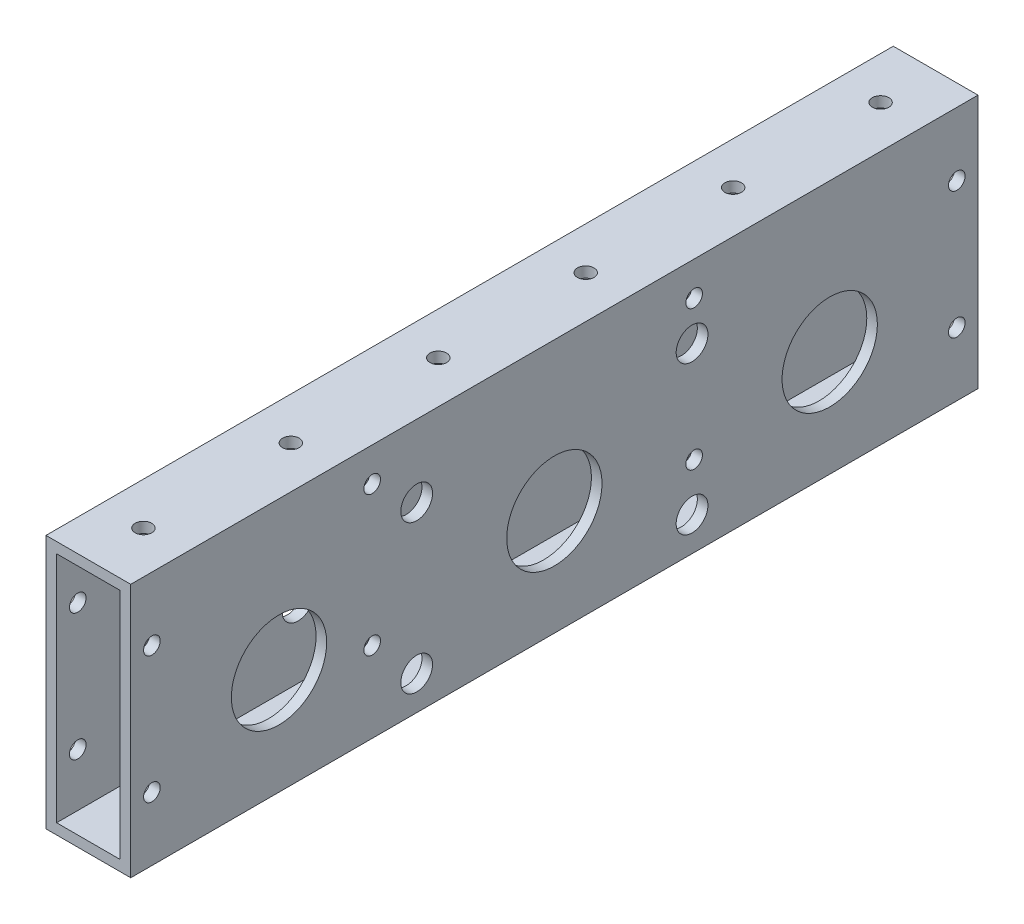
SolidWorks part; units mm, degrees
material "6061-T6 (SS)"
ref_plane "Front Plane" through (0, 0, 0) normal (0, 0, 1) x (1, 0, 0)
ref_plane "Top Plane" through (0, 0, 0) normal (0, 1, 0) x (1, 0, 0)
ref_plane "Right Plane" through (0, 0, 0) normal (1, 0, 0) x (0, 0, -1)
sketch "Sketch1" plane through (0, 0, 0) normal (1, 0, 0) x (0, 0, -1)
  line L1 (-127, 38.1) -> (127, 38.1)
  line L2 (-127, 38.1) -> (-127, -38.1)
  line L3 (-127, -38.1) -> (127, -38.1)
  line L4 (127, 38.1) -> (127, -38.1)
  line L5 (-127, 38.1) -> (127, -38.1) construction
  line L6 (-127, -38.1) -> (127, 38.1) construction
  point P0 (0, 0)
  dimension "D1" = 76.2
  dimension "D2" = 254
extrude "Boss-Extrude1" add sketch "Sketch1" along normal blind 25.4
shell "Shell1" thickness 3.175 removed face at (12.7, 0, -127) removed face at (12.7, 0, 127)
sketch "Sketch2" plane through (25.4, 0, 0) normal (1, 0, 0) x (0, 0, -1)
  line L0 (-127, -38.1) -> (127, -38.1) construction
  line L1 (127, 38.1) -> (-127, 38.1) construction
  line L2 (-41.275, -27.94) -> (41.275, -27.94) construction
  line L3 (-41.275, -27.94) -> (-41.275, 16.51) construction
  line L4 (-41.275, 16.51) -> (41.275, 16.51) construction
  line L5 (41.275, -27.94) -> (41.275, 16.51) construction
  line L6 (-41.275, -27.94) -> (41.275, 16.51) construction
  line L7 (-41.275, 16.51) -> (41.275, -27.94) construction
  line L9 (-54.61, 27.94) -> (41.91, 27.94) construction
  line L10 (-54.61, 27.94) -> (-54.61, -13.97) construction
  line L11 (-54.61, -13.97) -> (41.91, -13.97) construction
  line L12 (41.91, 27.94) -> (41.91, -13.97) construction
  circle A0 centre (0, -6.35) radius 14.2875
  circle A1 centre (-82.55, -6.35) radius 14.2875
  circle A2 centre (82.55, -6.35) radius 14.2875
  circle A3 centre (-82.55, -6.35) radius 38.1 construction
  circle A4 centre (0, -6.35) radius 38.1 construction
  circle A5 centre (82.55, -6.35) radius 38.1 construction
  circle A6 centre (-41.275, 16.51) radius 2.4892
  circle A7 centre (-41.275, -27.94) radius 2.4892
  circle A8 centre (41.275, -27.94) radius 2.4892
  circle A9 centre (41.275, 16.51) radius 2.4892
  circle A10 centre (-54.61, 27.94) radius 2.4892
  circle A11 centre (-54.61, -13.97) radius 2.4892
  circle A12 centre (41.91, -13.97) radius 2.4892
  circle A13 centre (41.91, 27.94) radius 2.4892
  point P11 (0, 0)
  point P12 (0, -5.715)
  dimension "D1" = 28.575
  dimension "D5" = 76.2
  dimension "D10" = 4.9784
  dimension "D2" = 31.75
  dimension "D3" = 82.55
  dimension "D4" = 82.55
  dimension "D6" = 0
  dimension "D7" = 10.16
  dimension "D8" = 21.59
  dimension "D9" = 82.55
  dimension "D11" = 10.16
  dimension "D12" = 96.52
  dimension "D13" = 41.91
  dimension "D14" = 24.13
extrude "Cut-Extrude1" cut sketch "Sketch2" against normal through all
sketch "Sketch3" plane through (25.4, 0, 0) normal (1, 0, 0) x (0, 0, -1)
  line L0 (-120.65, 19.05) -> (-120.65, -19.05) construction
  line L1 (-127, 38.1) -> (-127, -38.1) construction
  point P2 (-120.65, 0)
  point P3 (-127, 0)
  dimension "D1" = 38.1
  dimension "D2" = 6.35
hole_wizard "#10 Clearance Hole1" positions "Sketch4" profile "Sketch6" hole size "#10" standard "ANSI Inch" end condition through all
sketch "Sketch4" plane through (25.4, 0, 0) normal (1, 0, 0) x (0, 0, -1)
  point P0 (-120.65, 19.05)
  point P3 (-120.65, -19.05)
sketch "Sketch6" plane through (25.4, 19.05, 120.65) normal (0, 1, 0) x (0, 0, -1)
  line L0 (0, 0) -> (0, 25.4)
  line L1 (0, 25.4) -> (2.4892, 25.4)
  line L2 (2.4892, 25.4) -> (2.4892, 0)
  line L5 (2.4892, 0) -> (0, 0)
  line L11 (0, -6.35) -> (0, 107.95) construction
  dimension "Thru Hole Dia." = 4.9784
  dimension "Thru Hole Depth" = 25.4
mirror "Mirror1" about plane through (0, 0, 0) normal (0, 0, 1) of "#10 Clearance Hole1"
hole_wizard "3/8 (0.375) Diameter Hole1" positions "Sketch7" profile "Sketch8" hole size "3/8" standard "ANSI Inch"
sketch "Sketch7" plane through (0, 0, 0) normal (-1, 0, 0) x (0, 0, 1)
  point P0 (54.61, 27.94)
  point P3 (54.61, -13.97)
  point P6 (-41.91, -13.97)
  point P9 (-41.91, 27.94)
sketch "Sketch8" plane through (0, 27.94, 54.61) normal (0, 1, 0) x (0, 0, 1)
  line L0 (0, 0) -> (0, 13.7836)
  line L1 (0, 13.7836) -> (4.7625, 10.922)
  line L2 (4.7625, 10.922) -> (4.7625, 0)
  line L5 (4.7625, 0) -> (0, 0)
  line L10 (0, 13.7836) -> (-4.7625, 10.922) construction
  line L11 (0, -6.35) -> (0, 107.95) construction
  dimension "Hole Dia." = 9.525
  dimension "Hole Depth" = 10.922
  dimension "Drill Angle" = 118
hole_wizard "3/8 (0.375) Diameter Hole2" positions "Sketch9" profile "Sketch10" hole size "3/8" standard "ANSI Inch"
sketch "Sketch9" plane through (25.4, 0, 0) normal (1, 0, 0) x (0, 0, -1)
  point P0 (-41.275, 16.51)
  point P3 (-41.275, -27.94)
  point P6 (41.275, 16.51)
  point P9 (41.275, -27.94)
sketch "Sketch10" plane through (25.4, 16.51, 41.275) normal (0, 1, 0) x (0, 0, -1)
  line L0 (0, 0) -> (0, 13.7836)
  line L1 (0, 13.7836) -> (4.7625, 10.922)
  line L2 (4.7625, 10.922) -> (4.7625, 0)
  line L5 (4.7625, 0) -> (0, 0)
  line L10 (0, 13.7836) -> (-4.7625, 10.922) construction
  line L11 (0, -6.35) -> (0, 107.95) construction
  dimension "Hole Dia." = 9.525
  dimension "Hole Depth" = 10.922
  dimension "Drill Angle" = 118
sketch "Sketch11" plane through (0, -38.1, 0) normal (0, -1, 0) x (1, 0, 0)
  line L0 (25.4, -127) -> (0, -127) construction
  circle A0 centre (12.7, -110.49) radius 2.4892
  circle A1 centre (12.7, -66.294) radius 2.4892
  circle A2 centre (12.7, -22.098) radius 2.4892
  circle A3 centre (12.7, 22.098) radius 2.4892
  circle A4 centre (12.7, 66.294) radius 2.4892
  circle A5 centre (12.7, 110.49) radius 2.4892
  point P2 (12.7, -127)
  dimension "D2" = 4.9784
  dimension "D1" = 16.51
  dimension "D4" = 44.196
  dimension "D3" = 6
extrude "Cut-Extrude2" cut sketch "Sketch11" against normal through all
